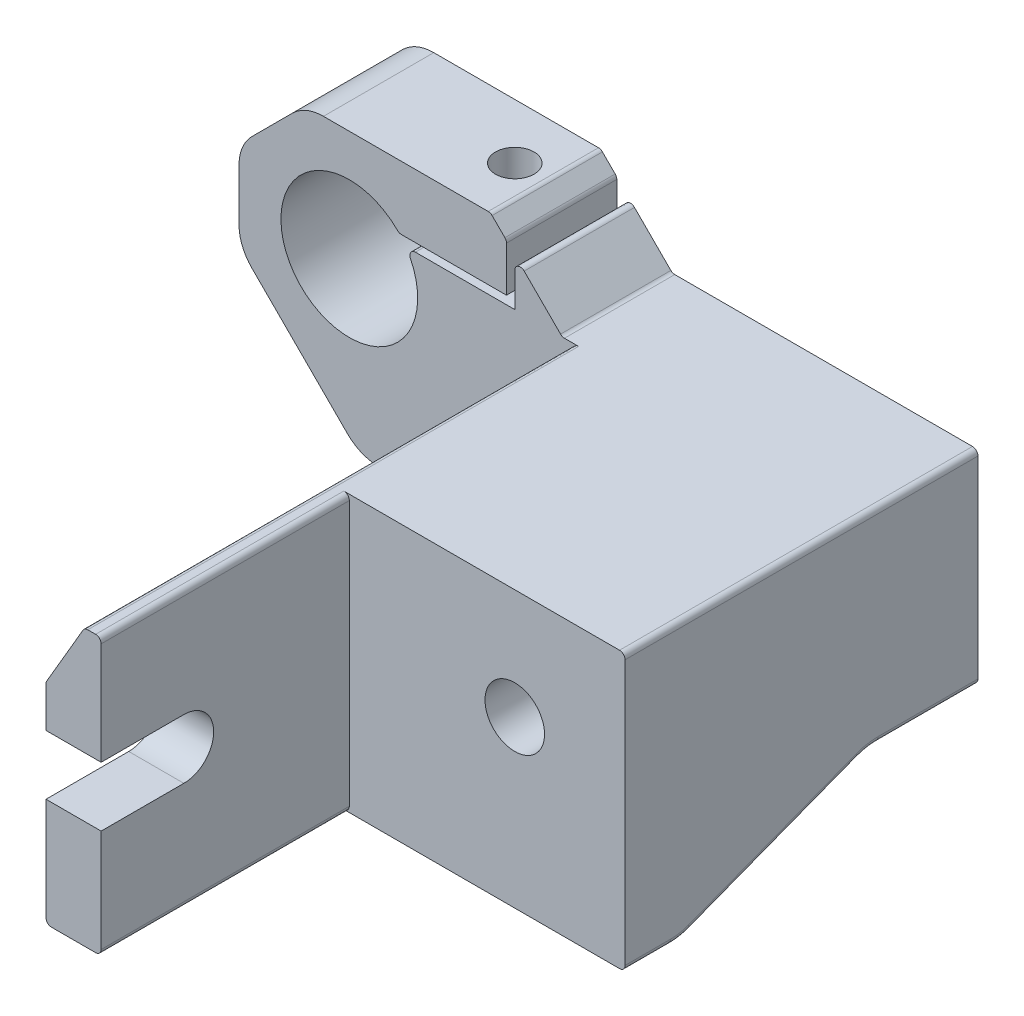
SolidWorks part; units mm, degrees
ref_plane "XY" through (0, 0, 0) normal (0, 0, 1) x (1, 0, 0)
ref_plane "XZ" through (0, 0, 0) normal (0, 1, 0) x (1, 0, 0)
ref_plane "YZ" through (0, 0, 0) normal (1, 0, 0) x (0, 0, -1)
sketch "Sketch1" plane through (0, 0, 0) normal (0, 0, 1) x (1, 0, 0)
  line L0 (-22.5, 15.75) -> (-28.5, 9.75)
  line L1 (-28.5, -9.25) -> (-17.5, -9.25) construction
  line L2 (-28.5, -9.25) -> (-28.5, 1.75) construction
  line L3 (-28.5, 9.25) -> (0.8, 9.25) construction
  line L4 (28.5, -9.25) -> (28.5, 9.25)
  line L5 (-28.5, -9.25) -> (28.5, 9.25) construction
  line L6 (-28.5, 9.25) -> (28.5, -9.25) construction
  line L7 (28.5, -15.75) -> (-28.5, -15.75) construction
  line L8 (28.5, -15.75) -> (28.5, 15.75) construction
  line L9 (28.5, 15.75) -> (-28.5, 15.75) construction
  line L10 (-28.5, -15.75) -> (-28.5, 15.75) construction
  line L11 (28.5, -15.75) -> (-28.5, 15.75) construction
  line L12 (28.5, 15.75) -> (-28.5, -15.75) construction
  line L13 (-5.7, 15.75) -> (-4.25, 14.3)
  line L14 (-5.7, 15.75) -> (-22.5, 15.75)
  line L15 (-17.5, -9.25) -> (-28.5, 1.75)
  line L16 (0.8, 9.25) -> (28.5, 9.25)
  line L17 (-28.5, 9.75) -> (-28.5, 9.25)
  line L18 (-28.5, 1.75) -> (-28.5, 9.25)
  line L19 (-17.5, -9.25) -> (28.5, -9.25)
  line L20 (-13.3824, 9.25) -> (-3.5, 9.25)
  line L21 (-3.5, 9.25) -> (-3.5, 13.55)
  line L22 (-13.9859, 10) -> (-4.25, 10)
  line L23 (-4.25, 10) -> (-4.25, 14.3)
  line L24 (-4.25, 10) -> (-4.25, 13.55) construction
  line L25 (-13.3824, 10) -> (-4.25, 10) construction
  line L26 (-3.5, 13.55) -> (0.8, 9.25)
  line L27 (-4.25, 14.3) -> (-3.5, 13.55) construction
  arc A0 (-13.9859, 10) -> (-13.3824, 9.25) centre (-18.5, 5.75) ccw
  arc A1 (-13.3824, 9.25) -> (-13.9859, 10) centre (-18.5, 5.75) ccw construction
  point P0 (0, 0)
  point P5 (0, 0)
  dimension "D10" = 18.5
  dimension "D12" = 12.4
  dimension "D1" = 57
  dimension "D2" = 18.5
  dimension "D3" = 31.5
  dimension "D4" = 45
  dimension "D5" = 6
  dimension "D6" = 45
  dimension "D7" = 45
  dimension "D8" = 22.8
  dimension "D9" = 11
  dimension "D11" = 5.75
  dimension "D13" = 3.5
  dimension "D14" = 0.75
extrude "Boss-Extrude1" add sketch "Sketch1" along normal blind 10
sketch "Sketch2" plane through (28.5, 0, 0) normal (1, 0, 0) x (0, 0, -1)
  line L0 (-10, 9.25) -> (-10, -9.25)
  line L1 (-10, -9.25) -> (-26.9331, -15.75)
  line L2 (-26.9331, -15.75) -> (-32, -15.75)
  line L3 (-32, -15.75) -> (-32, 9.25)
  line L4 (-32, 9.25) -> (-10, 9.25)
  dimension "D1" = 22
  dimension "D2" = 6.5
  dimension "D3" = 159
extrude "Boss-Extrude2" add sketch "Sketch2" against normal blind 30
sketch "Sketch3" plane through (0, 0, 32) normal (0, 0, 1) x (1, 0, 0)
  line L0 (-1.5, -15.75) -> (28.5, -15.75) construction
  line L1 (-1.5, 9.25) -> (3.5, 9.25)
  line L2 (-1.5, 9.25) -> (-1.5, -15.75)
  line L3 (-1.5, -15.75) -> (3.5, -15.75)
  line L4 (3.5, 9.25) -> (3.5, -15.75)
  dimension "D1" = 5
extrude "Boss-Extrude3" add sketch "Sketch3" along normal blind 22.5
sketch "Sketch4" plane through (0, 0, 0) normal (0, 0, -1) x (-1, 0, 0)
  circle A0 centre (-18.5, -0.75) radius 5.25
  dimension "D1" = 0.75
  dimension "D3" = 10.5
  dimension "D2" = 18.5
extrude "Cut-Extrude1" cut sketch "Sketch4" against normal blind 27
sketch "Sketch5" plane through (0, 0, 32) normal (0, 0, 1) x (1, 0, 0)
  circle A0 centre (18.5, -0.75) radius 2.7
  dimension "D1" = 5.4
extrude "Cut-Extrude3" cut sketch "Sketch5" against normal offset from surface (4.6 mm away) 0.4 up to face at (13.25, -0.75, 27)
sketch "Sketch6" plane through (0, 0, 54.5) normal (0, 0, 1) x (1, 0, 0)
  line L0 (-1.5, 9.25) -> (2, 9.25)
  line L1 (3.5, 9.25) -> (-1.5, 9.25) construction
  line L2 (2, 9.25) -> (-1.5, 3.25)
  line L3 (-1.5, 9.25) -> (-1.5, -15.75) construction
  line L4 (-1.5, 3.25) -> (-1.5, 9.25)
  dimension "D1" = 3.5
  dimension "D2" = 6
extrude "Cut-Extrude4" cut sketch "Sketch6" against normal up to surface (44.5 mm away) up to face at (-11.7439, 6.442, 10)
sketch "Sketch7" plane through (3.5, 0, 0) normal (1, 0, 0) x (0, 0, -1)
  line L0 (-47, -5.95) -> (-54.5, -5.95)
  line L1 (-54.5, -15.75) -> (-54.5, 9.25) construction
  line L2 (-54.5, -5.95) -> (-54.5, -0.55)
  line L3 (-54.5, -0.55) -> (-47, -0.55)
  arc A0 (-47, -5.95) -> (-47, -0.55) centre (-47, -3.25) ccw
  dimension "D1" = 3.25
  dimension "D2" = 47
  dimension "D3" = 5.4
extrude "Cut-Extrude5" cut sketch "Sketch7" against normal up to next
fillet "Fillet1" radius 4 4 edges at (-17.5, -9.25, 5) (-28.5, 1.75, 5) (-28.5, 9.75, 5) (-22.5, 15.75, 5)
fillet "Fillet2" radius 0.5 11 edges at (-1.5, 3.25, 32.25) (2, 9.25, 32.25) (-13.9859, 10, 5) (-13.3824, 9.25, 5) (-3.5, 13.55, 5) (-4.25, 14.3, 5) (28.5, 9.25, 16) (-5.7, 15.75, 5)
fillet "Fillet3" radius 5 2 edges at (13.5, -15.75, 26.9331)
fillet "Fillet4" radius 0.5 9 edges at (28.5, -15.75, 29.9299) (28.5, -15.6663, 26.9486) (28.5, -9.25, 4.5367) (28.5, -9.3337, 9.9845) (-1.5, -9.3337, 9.9845) (-1.5, -15.6663, 26.9486) (28.5, -12.5, 18.4665) (-1.5, -15.75, 41.1799)
ref_plane "Plane1" through (0, 0, 5) normal (0, 0, 1) x (1, 0, 0)
sketch "Sketch8" plane through (0, 0, 5) normal (0, 0, 1) x (1, 0, 0)
  line L0 (-8.5, 24.8529) -> (-8.5, -25.6111) construction
  line L1 (-8.5, 15.75) -> (-6.75, 15.75)
  line L2 (-5.9071, 15.75) -> (-20.8431, 15.75) construction
  line L3 (-6.75, 15.75) -> (-6.75, -4.25)
  line L4 (-6.75, -4.25) -> (-6.15, -4.25)
  line L5 (-6.15, -4.25) -> (-6.15, -8.75)
  line L6 (-6.15, -8.75) -> (-6, -8.75)
  line L7 (-6, -8.75) -> (-6, -9.25)
  line L8 (-15.8431, -9.25) -> (-1.2791, -9.25) construction
  line L9 (-6, -9.25) -> (-8.5, -9.25)
  line L10 (-8.5, -9.25) -> (-8.5, 15.75)
  dimension "D1" = 8.5
  dimension "D2" = 1.75
  dimension "D3" = 20
  dimension "D4" = 0.5
  dimension "D5" = 2.35
  dimension "D6" = 2.5
revolve "Cut-Revolve1" cut sketch "Sketch8" angle 360 about L0
